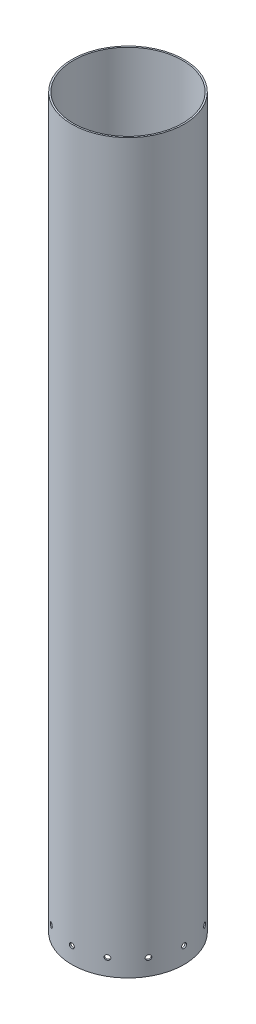
SolidWorks part; units mm, degrees
material "A-Glass Fiber"
ref_plane "Front Plane" through (0, 0, 0) normal (0, 0, 1) x (1, 0, 0)
ref_plane "Top Plane" through (0, 0, 0) normal (0, 1, 0) x (1, 0, 0)
ref_plane "Right Plane" through (0, 0, 0) normal (1, 0, 0) x (0, 0, -1)
sketch "Sketch1" plane through (0, 0, 0) normal (0, 1, 0) x (1, 0, 0)
  circle A0 centre (0, 0) radius 78.359
  circle A1 centre (0, 0) radius 76.2
  dimension "D1" = 152.4
  dimension "D2" = 156.718
extrude "Boss-Extrude1" add sketch "Sketch1" along normal blind 1016
ref_plane "Plane1" through (0, 0, 78.359) normal (0, 0, 1) x (1, 0, 0)
sketch "Sketch2" plane through (0, 0, 78.359) normal (0, 0, 1) x (1, 0, 0)
  line L0 (-78.359, 0) -> (78.359, 0) construction
  line L1 (-78.359, 0) -> (78.359, 0) construction
  line L2 (0, 0) -> (0, 1016) construction
  line L3 (78.359, 1016) -> (-78.359, 1016) construction
  line L4 (78.359, 1016) -> (-78.359, 1016) construction
  circle A0 centre (0, 22.86) radius 3.429
  point P9 (1.6218, 1016)
  dimension "D1" = 6.858
  dimension "D2" = 22.86
extrude "Cut-Extrude1" cut sketch "Sketch2" against normal up to next
pattern_circular "CirPattern1" count 12 over 360 about axis through (0, 0, 0) along (0, 1, 0) of "Cut-Extrude1"
